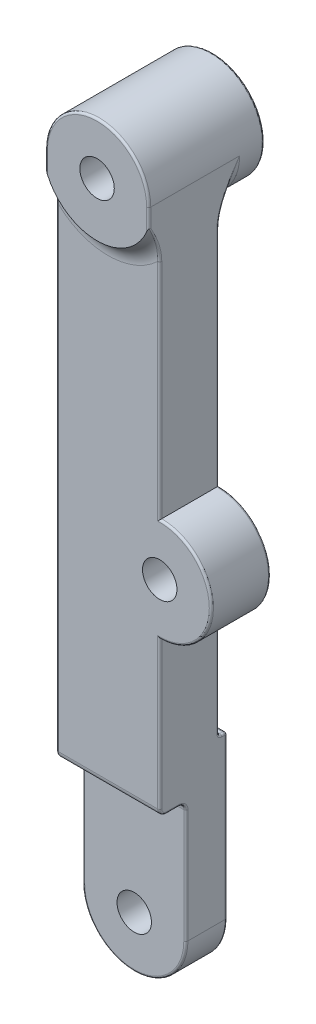
SolidWorks part; units mm, degrees
ref_plane "Front Plane" through (0, 0, 0) normal (0, 0, 1) x (1, 0, 0)
ref_plane "Top Plane" through (0, 0, 0) normal (0, 1, 0) x (1, 0, 0)
ref_plane "Right Plane" through (0, 0, 0) normal (1, 0, 0) x (0, 0, -1)
sketch "Sketch1" plane through (0, 0, 0) normal (0, 0, 1) x (1, 0, 0)
  line L0 (0, -47.5) -> (0, 47.5) construction
  line L1 (-7.5, -47.5) -> (-7.5, 47.5)
  line L2 (7.5, -47.5) -> (7.5, -7.5)
  line L3 (7.5, 7.5) -> (7.5, 47.5)
  arc A0 (-7.5, -47.5) -> (7.5, -47.5) centre (0, -47.5) ccw
  arc A1 (7.5, 47.5) -> (-7.5, 47.5) centre (0, 47.5) ccw
  arc A2 (7.5, -7.5) -> (7.5, 7.5) centre (7.5, 0) ccw
  circle A3 centre (7.5, 0) radius 2.5
  circle A4 centre (0, 47.5) radius 2.5
  circle A5 centre (0, -47.5) radius 2.5
  point P2 (0, 0)
  dimension "D2" = 7.5
  dimension "D4" = 15
  dimension "D5" = 5
  dimension "D1" = 95
  dimension "D3" = 47.5
  dimension "D6" = 47.5
extrude "Boss-Extrude1" add sketch "Sketch1" along normal blind 22
sketch "Sketch2" plane through (7.5, 0, 0) normal (1, 0, 0) x (0, 0, -1)
  line L0 (0, -61.4704) -> (0, 29.5) construction
  line L1 (0, 7.5) -> (0, 47.5) construction
  line L2 (-6.7, -61.4704) -> (-6.7, 29.5)
  line L3 (6.7, -61.4704) -> (6.7, 29.5)
  line L4 (-22, -61.4704) -> (-22, 29.5) construction
  line L6 (-22, 7.5) -> (-22, 47.5) construction
  line L7 (-28.7, -61.4704) -> (-28.7, 29.5)
  line L8 (-15.3, -61.4704) -> (-15.3, 29.5)
  line L9 (-22, 36.2) -> (-40.1391, 36.2) construction
  line L10 (-22, 47.5) -> (0, 47.5) construction
  line L11 (-22, 55.6) -> (-42.2672, 55.6) construction
  line L12 (-22, 55) -> (-22, 47.5) construction
  arc A0 (-6.7, -61.4704) -> (6.7, -61.4704) centre (0, -61.4704) ccw
  arc A1 (6.7, 29.5) -> (-6.7, 29.5) centre (0, 29.5) ccw
  arc A2 (-28.7, -61.4704) -> (-15.3, -61.4704) centre (-22, -61.4704) ccw
  arc A3 (-15.3, 29.5) -> (-28.7, 29.5) centre (-22, 29.5) ccw
  point P5 (0, -15.9852)
  point P11 (-22, -15.9852)
  dimension "D1" = 8.6
  dimension "D2" = 13.4
  dimension "D3" = 18
  dimension "D4" = 8.6
  dimension "D5" = 19.4
  dimension "D6" = 13.4
extrude "Cut-Extrude1" cut sketch "Sketch2" against normal mid plane 37
sketch "Sketch8" plane through (0, 0, 0) normal (1, 0, 0) x (0, 0, -1)
  line L0 (-60.5201, 47.5) -> (42.6618, 47.5) construction
  line L1 (-15.3, 29.5) -> (-15.3, 7.5) construction
  line L2 (-15.3, 25.9543) -> (-27.9269, 25.9543)
  line L3 (-15.3, 25.9543) -> (-15.3, 40)
  line L4 (-15.3, 40) -> (-27.9269, 40)
  line L5 (-27.9269, 25.9543) -> (-27.9269, 40)
  line L6 (0, 55) -> (-22, 55) construction
  line L7 (-11, 68.6979) -> (-11, -67.4374) construction
  line L8 (-6.7, 40) -> (5.9269, 40)
  line L9 (5.9269, 25.9543) -> (5.9269, 40)
  line L10 (-6.7, 25.9543) -> (5.9269, 25.9543)
  line L11 (-6.7, 25.9543) -> (-6.7, 40)
  dimension "D1" = 7.5
  dimension "D2" = 7.5
  dimension "D3" = 11
revolve "Cut-Revolve1" cut sketch "Sketch8" angle 360 about L0
fillet "Fillet2" radius 3 2 edges at (0, 40, 6.7) (0, 40, 15.3)
sketch "Sketch9" plane through (0, 0, 0) normal (1, 0, 0) x (0, 0, -1)
  line L1 (-26.9674, 65.5312) -> (-16.9, 65.5312)
  line L2 (-26.9674, 65.5312) -> (-26.9674, 33.4647)
  line L3 (-26.9674, 33.4647) -> (-16.9, 33.4647)
  line L4 (-16.9, 65.5312) -> (-16.9, 33.4647)
  line L5 (-15.3, -47.5) -> (-15.3, 40.1515) construction
  dimension "D1" = 1.6
extrude "Cut-Extrude2" cut sketch "Sketch9" against normal mid plane 34
sketch "Sketch12" plane through (-7.5, 0, 0) normal (-1, 0, 0) x (0, 0, 1)
  line L0 (16.9, 47.5) -> (16.9, 55) construction
  line L1 (0.1, 61.7771) -> (-16.679, 61.7771)
  line L2 (0.1, 61.7771) -> (0.1, 29.5751)
  line L3 (0.1, 29.5751) -> (-16.679, 29.5751)
  line L4 (-16.679, 61.7771) -> (-16.679, 29.5751)
  dimension "D1" = 16.8
extrude "Cut-Extrude3" cut sketch "Sketch12" against normal through all
sketch "Sketch13" plane through (0, 0, 0) normal (1, 0, 0) x (0, 0, -1)
  line L0 (-8.5, 69.6198) -> (-8.5, -73.4822) construction
  line L1 (-15.3, -47.5) -> (-15.3, 40.1515) construction
  line L2 (-6.7, 40.1515) -> (-6.7, -47.5) construction
  line L4 (-20.7698, -30) -> (-11.5, -30)
  line L5 (-20.7698, -30) -> (-20.7698, -67.4653)
  line L6 (-20.7698, -67.4653) -> (-11.5, -67.4653)
  line L7 (-11.5, -30) -> (-11.5, -67.4653)
  dimension "D1" = 6.8
  dimension "D2" = 1.8
  dimension "D3" = 3.8
  dimension "D4" = 30
extrude "Cut-Extrude4" cut sketch "Sketch13" against normal mid plane 20
sketch "Sketch14" plane through (0, 0, 6.7) normal (0, 0, -1) x (-1, 0, 0)
  line L0 (-7.5, -47.5) -> (-7.5, -24)
  line L1 (-7.5, -47.5) -> (-7.5, -7.5) construction
  line L2 (-7.5, -24) -> (7.5, -24)
  line L3 (7.5, 40.1515) -> (7.5, -47.5) construction
  line L4 (7.5, -24) -> (7.5, -47.5)
  arc A0 (-7.5, -47.5) -> (7.5, -47.5) centre (0, -47.5) ccw
  circle A1 centre (0, -47.5) radius 2.5
  dimension "D1" = 24
extrude "Boss-Extrude2" add sketch "Sketch14" along normal blind 1.2
fillet "Fillet3" radius 1 2 edges at (0, -30, 15.3) (0, -30, 11.5)
fillet "Fillet4" radius 0.4 2 edges at (0, -24, 5.5) (0, -24, 6.7)
fillet "Fillet5" radius 0.3 34 edges at (-7.5, 46.3467, 16.9) (7.5, 46.3467, 16.9) (7.5, 42.5159, 15.699) (7.5, -18.25, 15.3) (7.5, -29.7071, 15.0071) (7.5, -30, 13.4) (7.5, -30.2929, 11.7929) (7.5, -39.25, 11.5) (0, -55, 11.5) (-7.5, -39.25, 11.5) (-7.5, -30.2929, 11.7929) (-7.5, -30, 13.4) (-7.5, -29.7071, 15.0071) (-7.5, 42.5159, 15.699) (7.5, 42.5159, 6.301) (-7.5, 42.5159, 6.301) (7.5, -15.55, 6.7) (7.5, -23.8828, 6.5828) (7.5, -24, 6.1) (7.5, -24.1172, 5.6172) (7.5, -35.95, 5.5) (0, -55, 5.5) (-7.5, -35.95, 5.5) (-7.5, -24.1172, 5.6172) (-7.5, -24, 6.1) (-7.5, -23.8828, 6.5828) (0, 55, 16.9) (7.5, 23.8258, 15.3) (15, 0, 15.3) (-7.5, 5.5758, 15.3) (0, 40, 0.1) (7.5, 23.8258, 6.7) (15, 0, 6.7) (-7.5, 8.2758, 6.7)
